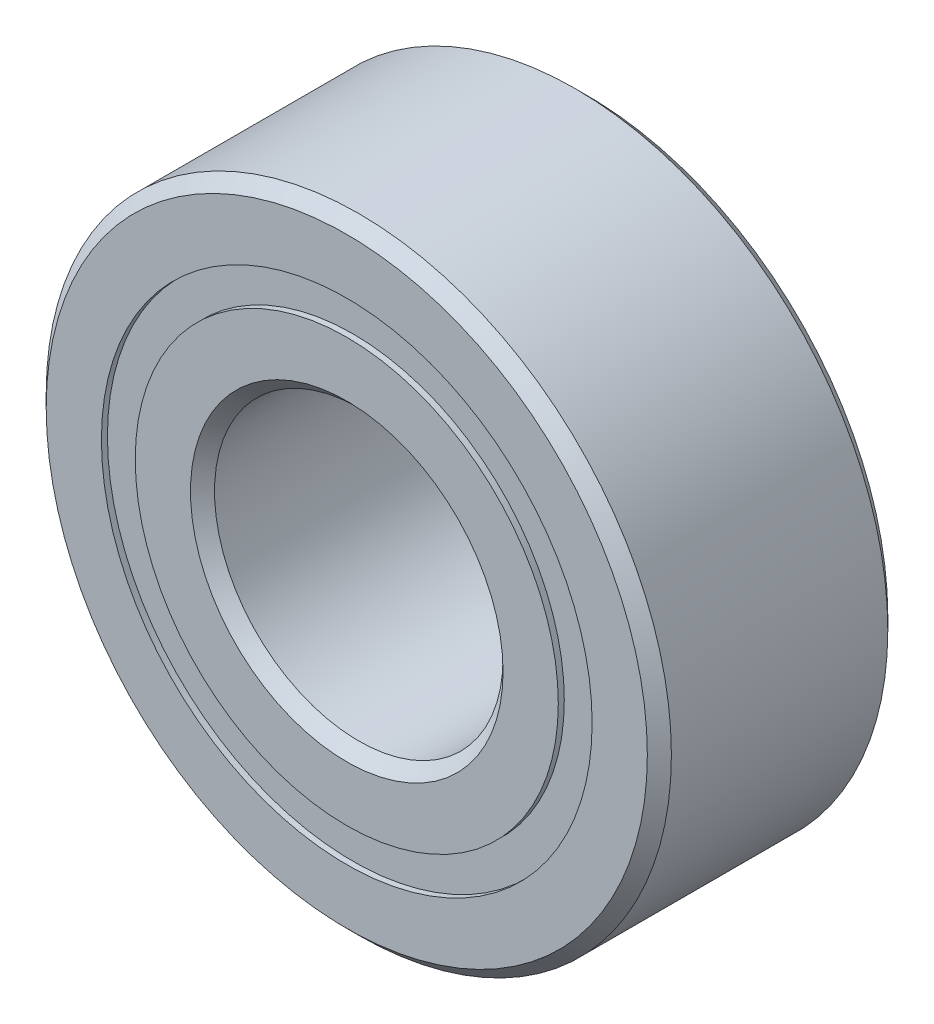
SolidWorks part; units mm, degrees
ref_plane "Front Plane" through (0, 0, 0) normal (0, 0, 1) x (1, 0, 0)
ref_plane "Top Plane" through (0, 0, 0) normal (0, 1, 0) x (1, 0, 0)
ref_plane "Right Plane" through (0, 0, 0) normal (1, 0, 0) x (0, 0, -1)
sketch "Sketch1" plane through (0, 0, 0) normal (1, 0, 0) x (0, 0, -1)
  line L0 (-2.5, 0) -> (2.5, 0) construction
  line L1 (0, 6.5) -> (0, -6.5) construction
  line L2 (2.25, 6.5) -> (-2.25, 6.5)
  line L3 (-2.25, 6.5) -> (-2.5, 6.25)
  line L4 (-2.5, 6.25) -> (-2.5, 5.1016)
  line L5 (-2.5, 5.1016) -> (-1.1111, 5.1016)
  line L6 (2.5, 5.1016) -> (1.1111, 5.1016)
  line L7 (2.5, 6.25) -> (2.5, 5.1016)
  line L8 (2.25, 6.5) -> (2.5, 6.25)
  line L9 (0, 6.5) -> (0, 4.75) construction
  line L10 (0, 4.75) -> (0, 3) construction
  arc A0 (-1.1111, 5.1016) -> (1.1111, 5.1016) centre (0, 4.75) cw
  point P14 (0, 3)
  dimension "Width" = 5
  dimension "OD" = 13
  dimension "D1" = 45
  dimension "D2" = 0.25
  dimension "Shaft Dia" = 6
  dimension "D3" = 2.2222
  dimension "D4" = 0.3516
revolve "Revolve1" add sketch "Sketch1" angle 360 about L0
sketch "Sketch3" plane through (0, 0, 0) normal (1, 0, 0) x (0, 0, -1)
  line L0 (-2.5, 4.3984) -> (-1.1111, 4.3984)
  line L1 (0, 6.5) -> (0, -6.5) construction
  line L2 (-2.5, 6.25) -> (-2.5, 5.1016) construction
  line L3 (-2.5, 4.3984) -> (-2.5, 3.25)
  line L4 (-2.25, 6.5) -> (-2.5, 6.25) construction
  line L5 (-2.5, 3.25) -> (-2.25, 3)
  line L6 (-2.25, 3) -> (2.25, 3)
  line L7 (2.25, 6.5) -> (2.25, -6.5) construction
  line L8 (2.25, 3) -> (2.5, 3.25)
  line L9 (2.5, -6.25) -> (2.5, 6.25) construction
  line L10 (2.5, 3.25) -> (2.5, 4.3984)
  line L11 (2.5, 4.3984) -> (1.1111, 4.3984)
  line L13 (2.25, 6.5) -> (2.5, 6.25) construction
  arc A0 (1.1111, 5.1016) -> (-1.1111, 5.1016) centre (0, 4.75) ccw construction
  arc A1 (1.1111, 4.3984) -> (-1.1111, 4.3984) centre (0, 4.75) cw
revolve "Revolve3" add sketch "Sketch3" angle 360 about L0
sketch "Sketch4" plane through (0, 0, 0) normal (1, 0, 0) x (0, 0, -1)
  line L0 (-1.1654, 4.75) -> (1.1654, 4.75)
  arc A2 (-1.1654, 4.75) -> (1.1654, 4.75) centre (0, 4.75) cw
  arc A3 (1.1111, 5.1016) -> (-1.1111, 5.1016) centre (0, 4.75) ccw construction
revolve "Revolve4" add sketch "Sketch4" angle 360 about L0
ref_axis "Axis1" through (0, 0, -2.5) along (0, 0, 1)
pattern_circular "CirPattern1" count 12 every 30 about axis through (0, 0, -2.5) along (0, 0, 1) of bodies 104
sketch "Sketch5" plane through (0, 0, 0) normal (1, 0, 0) x (0, 0, -1)
  line L0 (-2.5, 5.1016) -> (-1.1111, 5.1016) construction
  line L1 (-2.375, 5.1016) -> (-1.1654, 5.1016)
  line L2 (-2.375, 5.1016) -> (-2.375, 4.3984)
  line L3 (-2.375, 4.3984) -> (-1.1654, 4.3984)
  line L4 (-1.1654, 5.1016) -> (-1.1654, 4.3984)
  line L5 (-2.5, 4.3984) -> (-1.1111, 4.3984) construction
  line L6 (2.5, 5.1016) -> (1.1111, 5.1016) construction
  line L7 (2.375, 5.1016) -> (1.1654, 5.1016)
  line L8 (2.375, 5.1016) -> (2.375, 4.3984)
  line L9 (2.375, 4.3984) -> (1.1654, 4.3984)
  line L10 (1.1654, 5.1016) -> (1.1654, 4.3984)
  line L11 (2.5, 4.3984) -> (1.1111, 4.3984) construction
  line L12 (-2.25, 6.5) -> (-2.5, 6.25) construction
  point P18 (-2.375, 6.375)
revolve "Revolve5" add sketch "Sketch5" angle 360 about L0
sketch "Sketch6" plane through (0, 0, 0) normal (1, 0, 0) x (0, 0, -1)
  line L0 (2.5, 0) -> (-2.5, 0) construction
  line L1 (2.5, 5.1016) -> (1.4, 5.1016)
  line L2 (2.5, 5.1016) -> (2.5, 9.5)
  line L3 (2.5, 9.5) -> (1.4, 9.5)
  line L4 (1.4, 5.1016) -> (1.4, 9.5)
  dimension "Th" = 1.1
  dimension "Flange OD" = 19
revolve "Revolve6" [suppressed] add sketch "Sketch6" angle 360 about L0
equation "\"D2@Sketch1\" = \"Width@Sketch1\"*.05"
equation "\"D3@Sketch1\" = \"Width@Sketch1\"/2.25"
equation "\"D4@Sketch1\" = (((\"OD@Sketch1\"-\"Width@Sketch1\")/2)/3.25)/3.5"
equation "\"D2@CirPattern1\" = 360/\"Balls@CirPattern1\""
